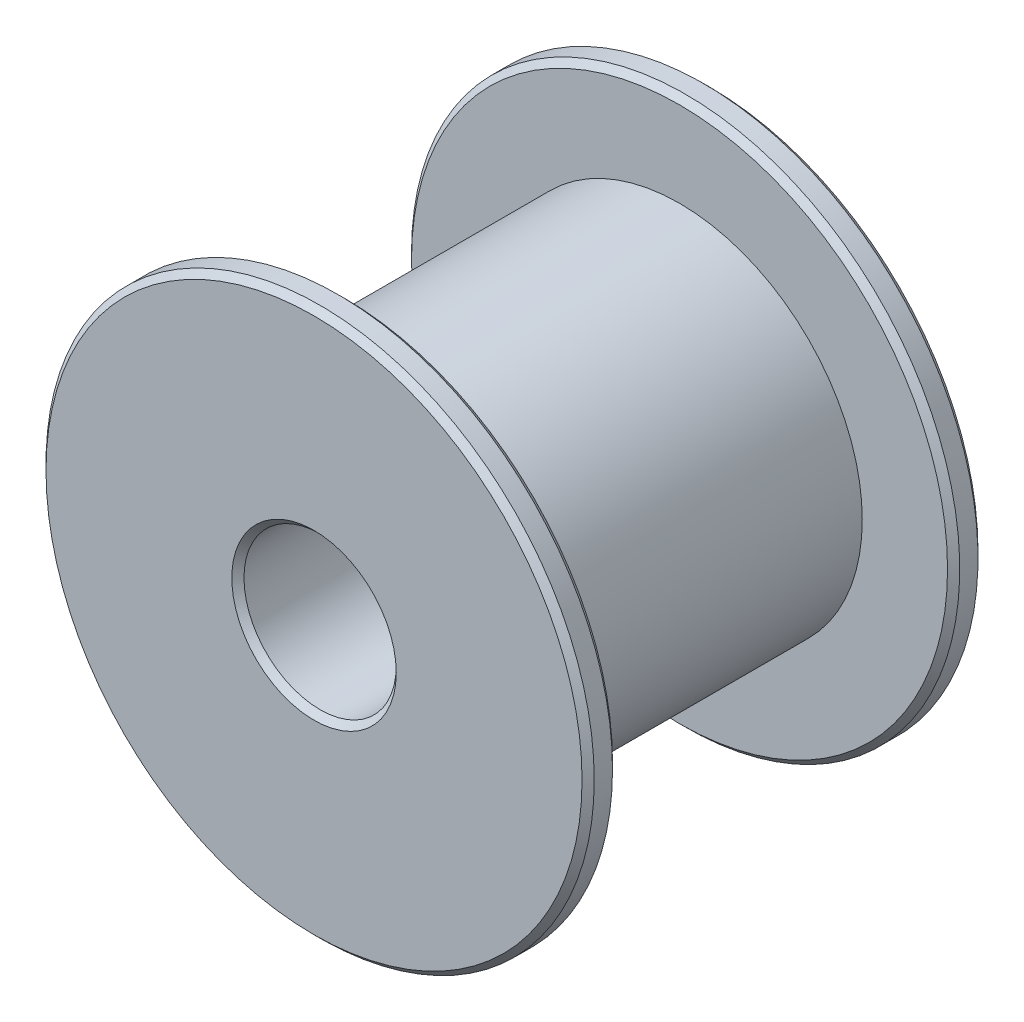
SolidWorks part; units mm, degrees
ref_plane "Front" through (0, 0, 0) normal (0, 0, 1) x (1, 0, 0)
ref_plane "Top" through (0, 0, 0) normal (0, 1, 0) x (1, 0, 0)
ref_plane "Right" through (0, 0, 0) normal (1, 0, 0) x (0, 0, -1)
sketch "Skizze1" plane through (0, 0, 0) normal (0, 0, 1) x (1, 0, 0)
  circle A0 centre (0, 0) radius 6
  dimension "D1" = 12
extrude "Aufsatz-Linear austragen1" add sketch "Skizze1" along normal mid plane 11
sketch "Skizze2" plane through (0, 0, 5.5) normal (0, 0, 1) x (1, 0, 0)
  circle A0 centre (0, 0) radius 9
  dimension "D1" = 18
extrude "Aufsatz-Linear austragen2" add sketch "Skizze2" along normal blind 1
mirror "Spiegeln1" about plane through (0, 0, 0) normal (0, 0, 1) of "Aufsatz-Linear austragen2"
sketch "Skizze3" plane through (0, 0, -6.5) normal (0, 0, -1) x (-1, 0, 0)
  circle A0 centre (0, 0) radius 2.5
  dimension "D1" = 5
extrude "Schnitt-Linear austragen1" cut sketch "Skizze3" against normal through all
chamfer "Fase1" distance 0.2 angle 45 6 edges at (-2.5, 0, -6.5) (-2.5, 0, 6.5) (9, 0, 6.5) (9, 0, 5.5) (9, 0, -5.5) (9, 0, -6.5)
sketch "Skizze4" plane through (0, 0, 6.5) normal (0, 0, 1) x (1, 0, 0)
  circle A0 centre (0, 0) radius 9.6375
extrude "Schnitt-Linear austragen2" [suppressed] cut sketch "Skizze4" against normal up to surface (1 mm away) up to face at (8.8, 0, 5.5)
